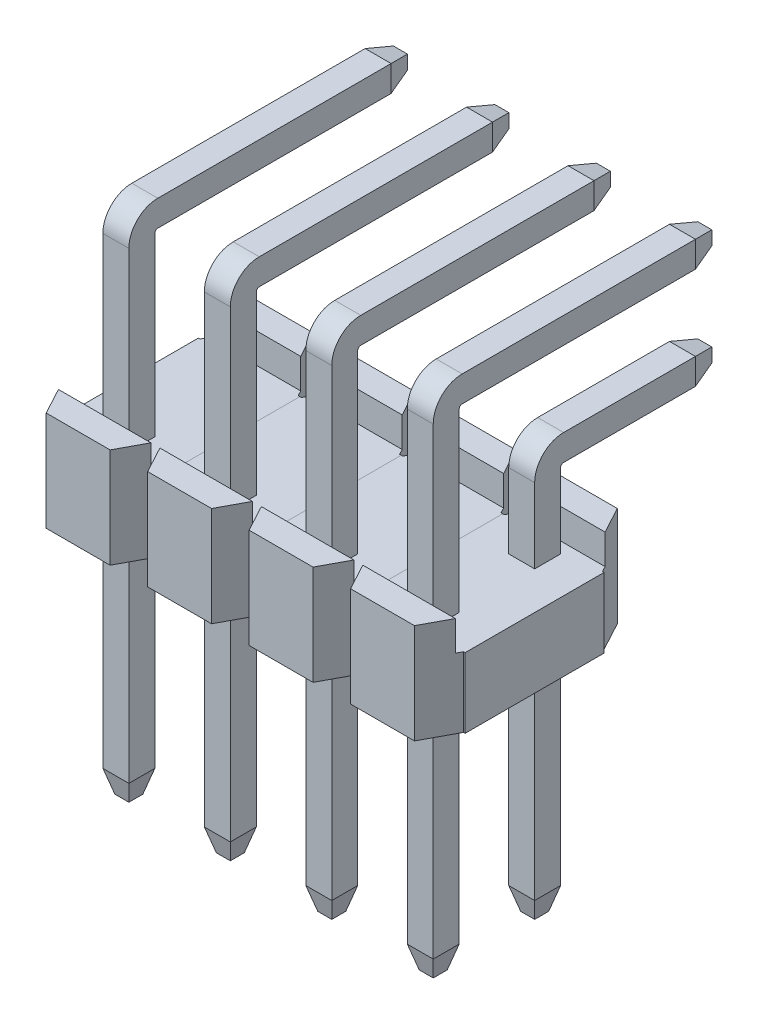
SolidWorks part; units mm, degrees
ref_plane "Спереди" through (0, 0, 0) normal (0, 0, 1) x (1, 0, 0)
ref_plane "Сверху" through (0, 0, 0) normal (0, 1, 0) x (1, 0, 0)
ref_plane "Справа" through (0, 0, 0) normal (1, 0, 0) x (0, 0, -1)
sketch "Эскиз1" plane through (0, 0, 0) normal (0, 1, 0) x (1, 0, 0)
  line L0 (-0.8, -5.08) -> (0.8, -5.08)
  line L1 (0.8, -5.08) -> (1.23, -4.28)
  line L2 (1.23, -4.28) -> (1.27, -4.28)
  line L3 (-1.27, -4.28) -> (-1.27, -0.8)
  line L4 (1.27, -4.28) -> (1.27, -0.8)
  line L5 (-1.23, -4.28) -> (-1.27, -4.28)
  line L6 (0, -2.54) -> (1.27, -2.54) construction
  line L7 (-0.8, -5.08) -> (-1.23, -4.28)
  line L8 (1.23, -0.8) -> (1.27, -0.8)
  line L9 (0.8, 0) -> (1.23, -0.8)
  line L10 (0, -5.08) -> (0, -2.54) construction
  line L11 (-0.8, 0) -> (0.8, 0)
  line L12 (-0.8, 0) -> (-1.23, -0.8)
  line L13 (-1.23, -0.8) -> (-1.27, -0.8)
  point P16 (-1.27, -2.54)
  dimension "D1" = 1.27
  dimension "D2" = 1.23
  dimension "D3" = 0.8
  dimension "D4" = 0.8
  dimension "D5" = 2.54
sketch "Эскиз3" plane through (0, 0, 0) normal (1, 0, 0) x (0, 0, -1)
  line L0 (2.99, 0) -> (-3.41, 0)
  line L1 (-3.81, -12.56) -> (-1.27, -12.56) construction
  line L2 (-3.81, -12.56) -> (-3.81, -0.4)
  line L5 (2.99, -2.54) -> (-0.87, -2.54) construction
  line L7 (-1.27, -12.56) -> (-1.27, -2.94) construction
  arc A1 (-3.41, 0) -> (-3.81, -0.4) centre (-3.41, -0.4) ccw
  arc A2 (-0.87, -2.54) -> (-1.27, -2.94) centre (-0.87, -2.94) ccw construction
  point P6 (-2.54, -12.56)
  dimension "D5" = 0.4
  dimension "D1" = 12.56
  dimension "D4" = 6.8
  dimension "D6" = 2.54
  dimension "D7" = 2.54
ref_plane "Плоскость1" through (0, -12.56, 0) normal (0, 1, 0) x (1, 0, 0)
sketch "Эскиз2" plane through (0, -12.56, 0) normal (0, 1, 0) x (1, 0, 0)
  line L1 (-0.325, -4.135) -> (0.325, -4.135)
  line L2 (-0.325, -4.135) -> (-0.325, -3.485)
  line L3 (-0.325, -3.485) -> (0.325, -3.485)
  line L4 (0.325, -4.135) -> (0.325, -3.485)
  line L5 (-0.325, -4.135) -> (0.325, -3.485) construction
  line L6 (-0.325, -3.485) -> (0.325, -4.135) construction
  line L7 (0, -3.81) -> (0, -1.27) construction
  line L8 (-0.325, -1.595) -> (0.325, -1.595) construction
  line L9 (-0.325, -1.595) -> (-0.325, -0.945) construction
  line L10 (-0.325, -0.945) -> (0.325, -0.945) construction
  line L11 (0.325, -1.595) -> (0.325, -0.945) construction
  line L12 (-0.325, -1.595) -> (0.325, -0.945) construction
  line L13 (-0.325, -0.945) -> (0.325, -1.595) construction
  point P0 (0, -3.81)
  point P7 (0, -1.27)
  dimension "D1" = 0.65
  dimension "D2" = 2.54
sketch "Эскиз4" plane through (0, -12.56, 0) normal (0, 1, 0) x (1, 0, 0)
  line L0 (0.325, -1.595) -> (0.325, -0.945) construction
  line L1 (-0.325, -1.595) -> (0.325, -1.595) construction
  line L2 (-0.325, -1.595) -> (-0.325, -0.945) construction
  line L3 (-0.325, -0.945) -> (0.325, -0.945) construction
  line L4 (0.325, -1.595) -> (0.325, -0.945)
  line L5 (-0.325, -1.595) -> (0.325, -1.595)
  line L6 (-0.325, -1.595) -> (-0.325, -0.945)
  line L7 (-0.325, -0.945) -> (0.325, -0.945)
sketch "Эскиз5" plane through (0, 0, 0) normal (1, 0, 0) x (0, 0, -1)
  line L0 (-1.27, -12.56) -> (-1.27, -2.94) construction
  line L1 (2.99, -2.54) -> (-0.87, -2.54) construction
  line L2 (-1.27, -12.56) -> (-1.27, -2.94)
  line L3 (2.99, -2.54) -> (-0.87, -2.54)
  arc A0 (-0.87, -2.54) -> (-1.27, -2.94) centre (-0.87, -2.94) ccw construction
  arc A1 (-0.87, -2.54) -> (-1.27, -2.94) centre (-0.87, -2.94) ccw
extrude "Бобышка-Вытянуть2" add sketch "Эскиз1" against normal blind 2.5 from offset 4.06 separate body offset against normal yes
sketch "Эскиз6" plane through (0, 0, 0) normal (0, 1, 0) x (1, 0, 0)
  line L0 (-1.27, -4.28) -> (-1.27, -0.8) construction
  line L1 (-1.27, -0.665) -> (1.27, -0.665)
  line L2 (-1.27, -0.665) -> (-1.27, -4.415)
  line L3 (-1.27, -4.415) -> (1.27, -4.415)
  line L4 (1.27, -0.665) -> (1.27, -4.415)
  line L5 (1.27, -4.28) -> (1.27, -0.8) construction
  dimension "D1" = 3.75
extrude "Вырез-Вытянуть1" cut sketch "Эскиз6" against normal blind 0.75 from offset 4.06 offset against normal yes
sweep "По траектории7" add profiles "Эскиз2" path "Эскиз3"
sweep "По траектории8" add profiles "Эскиз4" path "Эскиз5"
chamfer "Фаска5" distance 0.15 angle 75 4 edges at (0, -2.215, -2.99) (0.325, -2.54, -2.99) (0, -2.865, -2.99) (-0.325, -2.54, -2.99) first distance on face at (0, -2.54, -2.99)
chamfer "Фаска6" distance 0.15 angle 75 4 edges at (0.325, 0, -2.99) (0, 0.325, -2.99) (-0.325, 0, -2.99) (0, -0.325, -2.99) first distance on face at (0, 0, -2.99)
chamfer "Фаска7" distance 0.15 angle 75 4 edges at (0.325, -12.56, 3.81) (0, -12.56, 3.485) (-0.325, -12.56, 3.81) (0, -12.56, 4.135) first distance on face at (0, -12.56, 3.81)
chamfer "Фаска8" distance 0.15 angle 75 4 edges at (0.325, -12.56, 1.27) (0, -12.56, 0.945) (-0.325, -12.56, 1.27) (0, -12.56, 1.595) first distance on face at (0, -12.56, 1.27)
pattern_linear "Линейный массив1" count 4 spacing 2.54 along (1, 0, 0) of bodies 112
